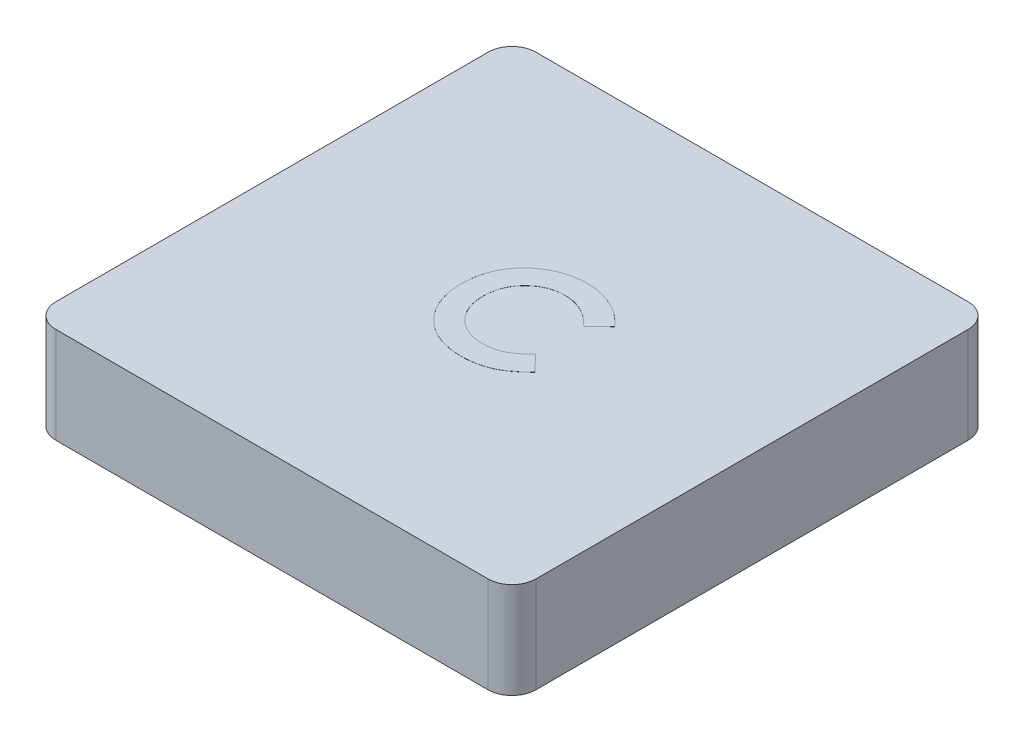
SolidWorks part; units mm, degrees
ref_plane "Front Plane" through (0, 0, 0) normal (0, 0, 1) x (1, 0, 0)
ref_plane "Top Plane" through (0, 0, 0) normal (0, 1, 0) x (1, 0, 0)
ref_plane "Right Plane" through (0, 0, 0) normal (1, 0, 0) x (0, 0, -1)
sketch "Sketch1" plane through (0, 0, 0) normal (0, 1, 0) x (1, 0, 0)
  line L0 (0, 0) -> (12.7, 0)
  line L1 (12.7, 0) -> (12.7, 12.7)
  line L2 (12.7, 12.7) -> (0, 12.7)
  line L3 (0, 12.7) -> (0, 0)
  dimension "D1" = 12.7
  dimension "D2" = 12.7
extrude "Boss-Extrude1" add sketch "Sketch1" along normal blind 2.54
fillet "Fillet1" radius 0.635 4 edges at (0, 1.27, -12.7) (12.7, 1.27, -12.7) (12.7, 1.27, 0) (0, 1.27, 0)
shell "Shell1" thickness 0.635 removed face at (6.35, 0, -6.35)
sketch "Sketch2" plane through (0, 1.905, 0) normal (0, -1, 0) x (-1, 0, 0)
  line L0 (-0.635, 6.35) -> (-12.065, 6.35) construction
  line L1 (-0.635, 12.065) -> (-0.635, 0.635) construction
  line L2 (-12.065, 0.635) -> (-12.065, 12.065) construction
  line L3 (-6.35, 0.635) -> (-6.35, 12.065) construction
  line L4 (-0.635, 0.635) -> (-12.065, 0.635) construction
  line L5 (-12.065, 12.065) -> (-0.635, 12.065) construction
  circle A0 centre (-6.35, 6.35) radius 2.54
  dimension "D1" = 5.08
extrude "Boss-Extrude2" add sketch "Sketch2" along normal up to surface (1.905 mm away) up to face at (6.35, 0, -6.35)
sketch "Sketch3" plane through (0, 2.54, 0) normal (0, 1, 0) x (1, 0, 0)
  line L0 (0, 12.065) -> (0, 0.635) construction
  line L1 (0.635, 0) -> (12.065, 0) construction
  text T0 "<b>C</b>"
  point P1 (0, 0)
  dimension "D1" = 4.7498
  dimension "D2" = 4.826
extrude "Boss-Extrude3" add sketch "Sketch3" along normal blind 0.0025
